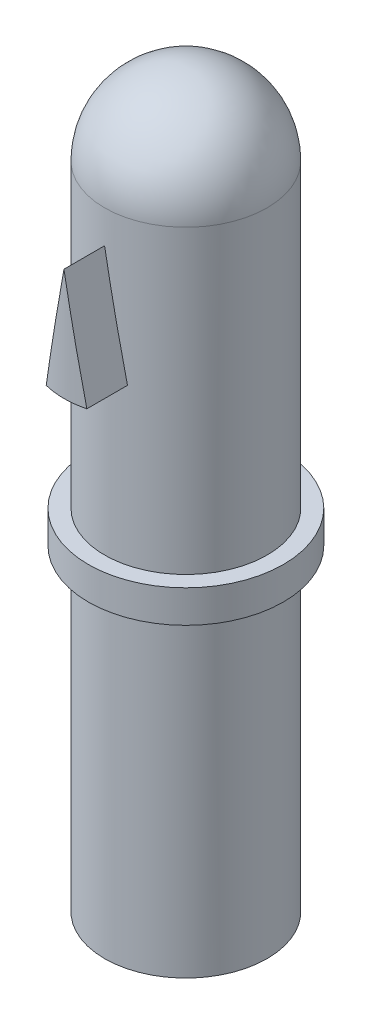
SolidWorks part; units mm, degrees
ref_plane "Front Plane" through (0, 0, 0) normal (0, 0, 1) x (1, 0, 0)
ref_plane "Top Plane" through (0, 0, 0) normal (0, 1, 0) x (1, 0, 0)
ref_plane "Right Plane" through (0, 0, 0) normal (1, 0, 0) x (0, 0, -1)
sketch "Sketch1" plane through (0, 0, 0) normal (0, 1, 0) x (1, 0, 0)
  circle A0 centre (0, 0) radius 10
extrude "Boss-Extrude1" add sketch "Sketch1" along normal blind 80
sketch "Sketch2" plane through (0, 0, 0) normal (0, 0, 1) x (1, 0, 0)
  line L0 (0, 75.9639) -> (-2.5, 62.1786)
  line L1 (-2.5, 62.1786) -> (2.5, 62.1786)
  line L2 (2.5, 62.1786) -> (0, 75.9639)
  dimension "D1" = 5
  dimension "D2" = 2.5
  dimension "D3" = 2.5
extrude "Boss-Extrude2" add sketch "Sketch2" along normal blind 5 from surface starting at face at (0, 80, 10)
sketch "Sketch3" plane through (0, 0, 0) normal (0, -1, 0) x (1, 0, 0)
  circle A0 centre (0, 0) radius 12
extrude "Boss-Extrude3" add sketch "Sketch3" along normal blind 4 from offset 43 offset against normal yes
dome "Dome1" faces to dome 1 distance 10 reverse direction no elliptical dome no face at (0, 80, 10) parameters "D1"=10
